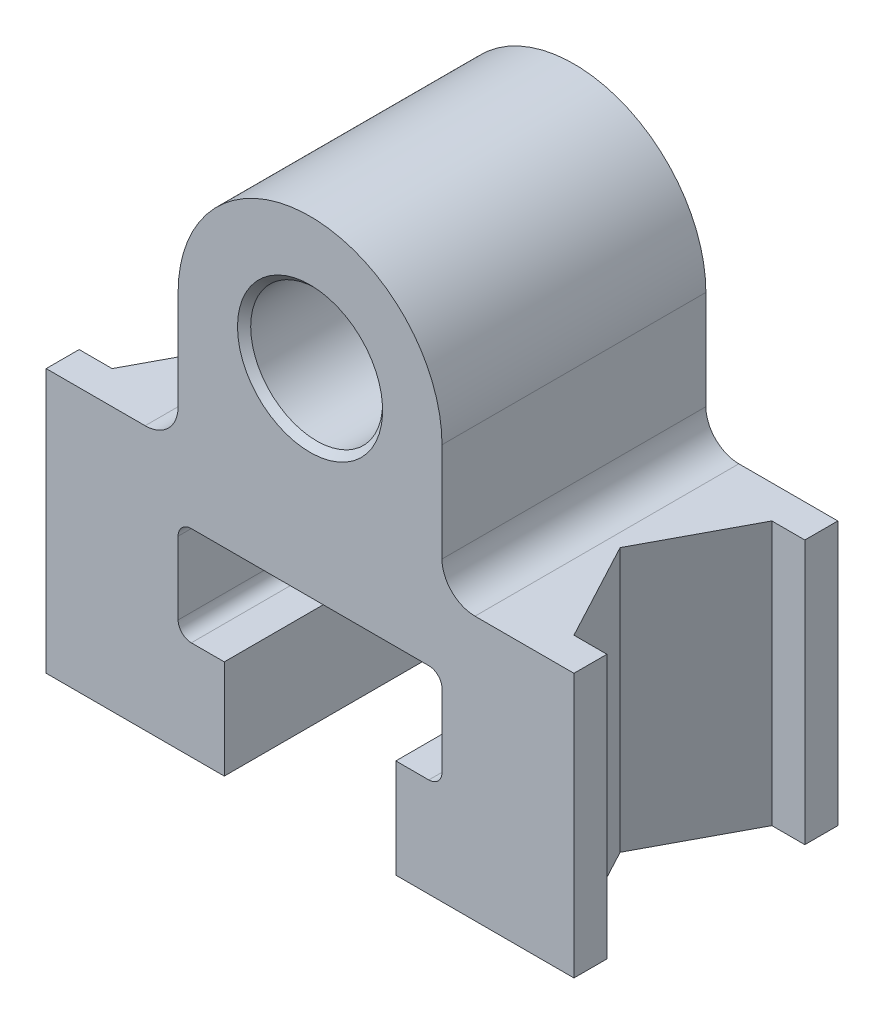
SolidWorks part; units mm, degrees
material "AISI 1020"
ref_plane "Plano frontal" through (0, 0, 0) normal (0, 0, 1) x (1, 0, 0)
ref_plane "Plano superior" through (0, 0, 0) normal (0, 1, 0) x (1, 0, 0)
ref_plane "Plano direito" through (0, 0, 0) normal (1, 0, 0) x (0, 0, -1)
sketch "Esboço1" plane through (0, 0, 0) normal (0, 1, 0) x (1, 0, 0)
  line L1 (-40, -20) -> (40, -20)
  line L2 (-40, -20) -> (-40, 20)
  line L3 (-40, 20) -> (40, 20)
  line L4 (40, -20) -> (40, 20)
  line L5 (-40, -20) -> (40, 20) construction
  line L6 (-40, 20) -> (40, -20) construction
  point P0 (0, 0)
  dimension "D1" = 80
  dimension "D2" = 40
extrude "Ressalto-extrusão1" add sketch "Esboço1" along normal blind 80
sketch "Esboço2" plane through (0, 0, 20) normal (0, 0, 1) x (1, 0, 0)
  line L1 (-40, 80) -> (-20, 80)
  line L2 (-40, 80) -> (-40, 40)
  line L3 (-40, 40) -> (-20, 40)
  line L4 (-20, 80) -> (-20, 40)
  line L5 (40, 80) -> (20, 80)
  line L6 (40, 80) -> (40, 40)
  line L7 (40, 40) -> (20, 40)
  line L8 (20, 80) -> (20, 40)
  point P10 (0, 0)
  dimension "D1" = 40
  dimension "D2" = 20
  dimension "D3" = 20
  dimension "D4" = 40
extrude "Corte-extrusão1" cut sketch "Esboço2" against normal blind 80
fillet "Filete1" 2 edges at (20, 80, 0) (-20, 80, 0) type full round first side face at (20, 60, 0) second side face at (-20, 60, 0) middle face at (0, 80, 0) tangent propagation no
hole_wizard "Furo de diâmetro Ø20.0 (20)1" positions "Esboço3" profile "Esboço4" hole size "Ø20.0" standard "DIN" end condition through all
sketch "Esboço3" plane through (0, 0, 20) normal (0, 0, 1) x (1, 0, 0)
  point P0 (0, 60)
sketch "Esboço4" plane through (0, 60, 20) normal (1, 0, 0) x (0, -1, 0)
  line L0 (0, 0) -> (0, 40)
  line L1 (0, 40) -> (10, 40)
  line L2 (10, 40) -> (10, 0)
  line L5 (10, 0) -> (0, 0)
  line L11 (0, -6.35) -> (0, 107.95) construction
  dimension "Thru Hole Dia." = 20
  dimension "Thru Hole Depth" = 40
chamfer "Chanfro1" distance 1 angle 45 2 edges at (10, 60, -20) (10, 60, 20)
sketch "Esboço5" plane through (0, 40, 0) normal (0, 1, 0) x (1, 0, 0)
  line L0 (40, 15) -> (35, 15)
  line L1 (40, 20) -> (40, -20) construction
  line L2 (35, 15) -> (27, 0)
  line L3 (27, 0) -> (35, -15)
  line L4 (35, -15) -> (40, -15)
  line L5 (40, 15) -> (40, -15)
  line L6 (20, 20) -> (40, 20) construction
  line L7 (20, -20) -> (40, -20) construction
  line L8 (-20, -20) -> (20, -20) construction
  point P13 (26.2193, -7.1898)
  point P18 (27.3111, 0.9013)
  dimension "D1" = 5
  dimension "D2" = 5
  dimension "D3" = 13
  dimension "D4" = 20
  dimension "D5" = 5
  dimension "D6" = 5
extrude "Corte-extrusão2" cut sketch "Esboço5" against normal blind 80 contours L2 L3 L4 L5 L0
mirror "Espelhar1" about plane through (0, 0, 0) normal (1, 0, 0) of "Corte-extrusão2"
sketch "Esboço6" plane through (0, 0, 20) normal (0, 0, 1) x (1, 0, 0)
  line L0 (-13, 0) -> (-13, 15)
  line L1 (-40, 0) -> (40, 0) construction
  line L2 (-13, 15) -> (-20, 15)
  line L3 (-20, 15) -> (-20, 30)
  line L4 (-20, 30) -> (20, 30)
  line L5 (20, 30) -> (20, 15)
  line L6 (20, 15) -> (13, 15)
  line L7 (13, 15) -> (13, 0)
  line L8 (13, 0) -> (-13, 0)
  point P7 (0, 0)
  dimension "D1" = 20
  dimension "D2" = 40
  dimension "D3" = 7
  dimension "D4" = 30
  dimension "D5" = 15
  dimension "D6" = 26
extrude "Corte-extrusão3" cut sketch "Esboço6" against normal blind 80
fillet "Filete2" radius 2 4 edges at (-20, 15, 0) (-20, 30, 0) (20, 15, 0) (20, 30, 0)
fillet "Filete3" radius 5 2 edges at (20, 40, 0) (-20, 40, 0)
